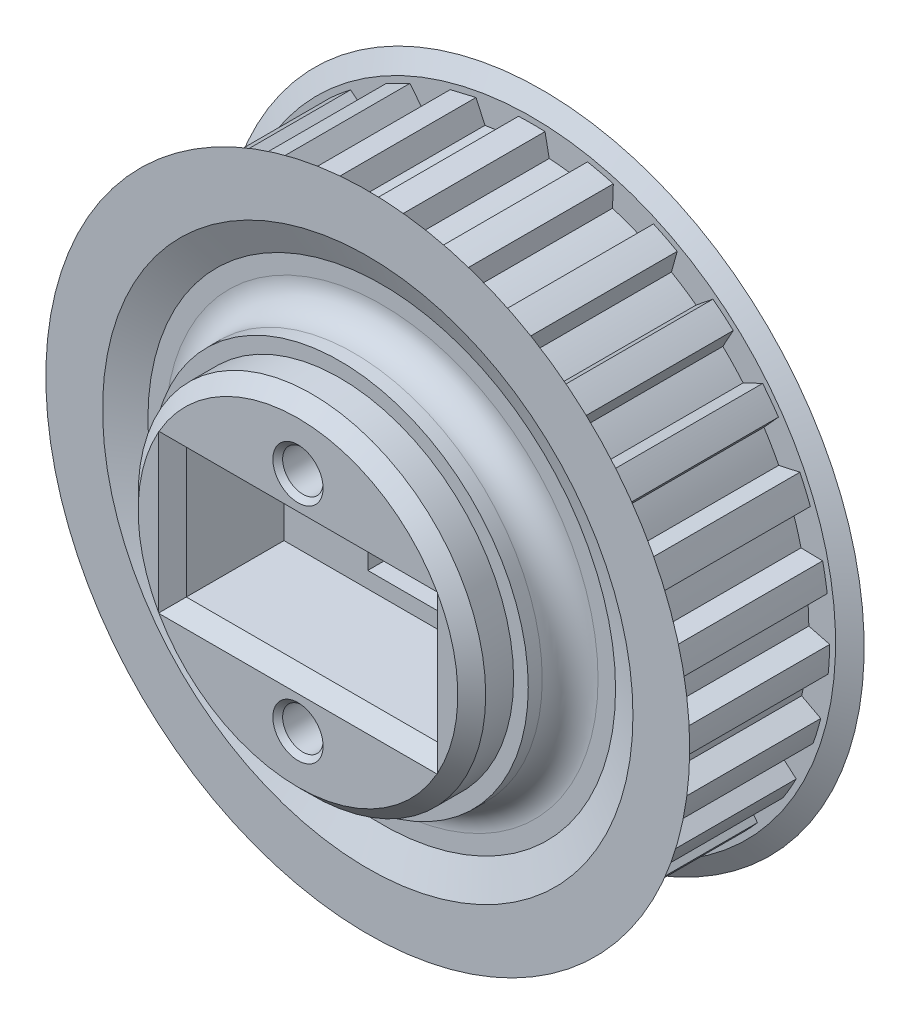
SolidWorks part; units mm, degrees
other "Markup1"
sketch "Sketch8" plane through (-22.8072, 22.8072, -5) normal (-0.0228, 0.8013, -0.5978) x (-0.0343, -0.5983, -0.8006)
material "ABS"
ref_plane "Alzado" through (0, 0, 0) normal (0, 0, 1) x (1, 0, 0)
ref_plane "Planta" through (0, 0, 0) normal (0, 1, 0) x (1, 0, 0)
ref_plane "Vista lateral" through (0, 0, 0) normal (1, 0, 0) x (0, 0, -1)
sketch "Croquis1" plane through (0, 0, 0) normal (0, 0, 1) x (1, 0, 0)
  line L0 (0, 0) -> (0, 14.5885) construction
  line L1 (-0.95, 21.3289) -> (-1.25, 19.8106)
  line L2 (0.95, 21.3289) -> (1.25, 19.8106)
  line L3 (5.8432, 20.5348) -> (5.7849, 18.9883)
  line L4 (3.9944, 20.973) -> (3.3523, 19.5649)
  line L5 (10.4213, 18.6338) -> (10.008, 17.1424)
  line L6 (8.7234, 19.4865) -> (7.7739, 18.2644)
  line L7 (14.4377, 15.7282) -> (13.6916, 14.3723)
  line L8 (12.9822, 16.9495) -> (11.7765, 15.9793)
  line L9 (17.6757, 11.9747) -> (16.637, 10.8274)
  line L10 (16.5411, 13.4987) -> (15.1441, 12.8327)
  line L11 (19.9608, 7.5756) -> (18.6855, 6.6988)
  line L12 (19.2082, 9.3202) -> (17.6953, 8.9943)
  line L13 (21.1698, 2.7681) -> (19.7267, 2.2091)
  line L14 (20.8399, 4.6393) -> (19.2926, 4.6711)
  line L15 (21.2375, -2.1886) -> (19.7044, -2.3998)
  line L16 (21.348, -0.2918) -> (19.8498, 0.096)
  line L17 (20.1604, -7.0273) -> (18.6198, -6.8792)
  line L18 (20.7053, -5.2071) -> (19.3369, -4.4843)
  line L19 (17.9963, -11.4872) -> (16.5315, -10.9878)
  line L20 (18.9463, -9.8417) -> (17.7815, -8.8228)
  line L21 (14.8621, -15.3278) -> (13.5519, -14.5041)
  line L22 (16.166, -13.9457) -> (15.2675, -12.6856)
  line L23 (10.9267, -18.342) -> (9.8417, -17.2384)
  line L24 (12.5141, -17.298) -> (11.9305, -15.8646)
  line L25 (6.4022, -20.3675) -> (5.601, -19.0434)
  line L26 (8.1876, -19.7176) -> (7.9502, -18.1884)
  line L27 (1.5326, -21.2949) -> (1.0583, -19.8218)
  line L28 (3.4197, -21.0743) -> (3.5414, -19.5315)
  line L29 (-3.4197, -21.0743) -> (-3.5414, -19.5315)
  line L30 (-1.5326, -21.2949) -> (-1.0583, -19.8218)
  line L31 (-8.1876, -19.7176) -> (-7.9502, -18.1884)
  line L32 (-6.4022, -20.3675) -> (-5.601, -19.0434)
  line L33 (-12.5141, -17.298) -> (-11.9305, -15.8646)
  line L34 (-10.9267, -18.342) -> (-9.8417, -17.2384)
  line L35 (-16.166, -13.9457) -> (-15.2675, -12.6856)
  line L36 (-14.8621, -15.3278) -> (-13.5519, -14.5041)
  line L37 (-18.9463, -9.8417) -> (-17.7815, -8.8228)
  line L38 (-17.9963, -11.4872) -> (-16.5315, -10.9878)
  line L39 (-20.7053, -5.2071) -> (-19.3369, -4.4843)
  line L40 (-20.1604, -7.0273) -> (-18.6198, -6.8792)
  line L41 (-21.348, -0.2918) -> (-19.8498, 0.096)
  line L42 (-21.2375, -2.1886) -> (-19.7044, -2.3998)
  line L43 (-20.8399, 4.6393) -> (-19.2926, 4.6711)
  line L44 (-21.1698, 2.7681) -> (-19.7267, 2.2091)
  line L45 (-19.2082, 9.3202) -> (-17.6953, 8.9943)
  line L46 (-19.9608, 7.5756) -> (-18.6855, 6.6988)
  line L47 (-16.5411, 13.4987) -> (-15.1441, 12.8327)
  line L48 (-17.6757, 11.9747) -> (-16.637, 10.8274)
  line L49 (-12.9822, 16.9495) -> (-11.7765, 15.9793)
  line L50 (-14.4377, 15.7282) -> (-13.6916, 14.3723)
  line L51 (-8.7234, 19.4865) -> (-7.7739, 18.2644)
  line L52 (-10.4213, 18.6338) -> (-10.008, 17.1424)
  line L53 (-10.4213, 18.6338) -> (-8.7234, 19.4865)
  line L54 (-3.9944, 20.973) -> (-3.3523, 19.5649)
  line L55 (-5.8432, 20.5348) -> (-5.7849, 18.9883)
  line L56 (-5.8432, 20.5348) -> (-3.9944, 20.973)
  arc A0 (-10.008, 17.1424) -> (-11.7765, 15.9793) centre (0, 0) ccw
  arc A1 (3.3523, 19.5649) -> (1.25, 19.8106) centre (0, 0) ccw
  arc A2 (-5.7849, 18.9883) -> (-7.7739, 18.2644) centre (0, 0) ccw
  arc A9 (-12.9822, 16.9495) -> (-14.4377, 15.7282) centre (0, 0) ccw
  arc A10 (-16.5411, 13.4987) -> (-17.6757, 11.9747) centre (0, 0) ccw
  arc A11 (5.8432, 20.5348) -> (3.9944, 20.973) centre (0, 0) ccw
  arc A12 (0.95, 21.3289) -> (-0.95, 21.3289) centre (0, 0) ccw
  arc A16 (10.4213, 18.6338) -> (8.7234, 19.4865) centre (0, 0) ccw
  arc A17 (14.4377, 15.7282) -> (12.9822, 16.9495) centre (0, 0) ccw
  arc A18 (17.6757, 11.9747) -> (16.5411, 13.4987) centre (0, 0) ccw
  arc A19 (19.9608, 7.5756) -> (19.2082, 9.3202) centre (0, 0) ccw
  arc A20 (21.1698, 2.7681) -> (20.8399, 4.6393) centre (0, 0) ccw
  arc A21 (21.2375, -2.1886) -> (21.348, -0.2918) centre (0, 0) ccw
  arc A22 (20.1604, -7.0273) -> (20.7053, -5.2071) centre (0, 0) ccw
  arc A23 (17.9963, -11.4872) -> (18.9463, -9.8417) centre (0, 0) ccw
  arc A24 (14.8621, -15.3278) -> (16.166, -13.9457) centre (0, 0) ccw
  arc A25 (10.9267, -18.342) -> (12.5141, -17.298) centre (0, 0) ccw
  arc A26 (-8.1876, -19.7176) -> (-6.4022, -20.3675) centre (0, 0) ccw
  arc A27 (-12.5141, -17.298) -> (-10.9267, -18.342) centre (0, 0) ccw
  arc A28 (-16.166, -13.9457) -> (-14.8621, -15.3278) centre (0, 0) ccw
  arc A29 (-20.7053, -5.2071) -> (-20.1604, -7.0273) centre (0, 0) ccw
  arc A30 (-21.348, -0.2918) -> (-21.2375, -2.1886) centre (0, 0) ccw
  arc A31 (-20.8399, 4.6393) -> (-21.1698, 2.7681) centre (0, 0) ccw
  arc A32 (-19.2082, 9.3202) -> (-19.9608, 7.5756) centre (0, 0) ccw
  arc A33 (-3.4197, -21.0743) -> (-1.5326, -21.2949) centre (0, 0) ccw
  arc A34 (1.5326, -21.2949) -> (3.4197, -21.0743) centre (0, 0) ccw
  arc A35 (6.4022, -20.3675) -> (8.1876, -19.7176) centre (0, 0) ccw
  arc A36 (7.7739, 18.2644) -> (5.7849, 18.9883) centre (0, 0) ccw
  arc A37 (11.7765, 15.9793) -> (10.008, 17.1424) centre (0, 0) ccw
  arc A39 (-1.25, 19.8106) -> (-3.3523, 19.5649) centre (0, 0) ccw
  arc A43 (15.1441, 12.8327) -> (13.6916, 14.3723) centre (0, 0) ccw
  arc A44 (17.6953, 8.9943) -> (16.637, 10.8274) centre (0, 0) ccw
  arc A45 (19.2926, 4.6711) -> (18.6855, 6.6988) centre (0, 0) ccw
  arc A46 (19.8498, 0.096) -> (19.7267, 2.2091) centre (0, 0) ccw
  arc A47 (19.3369, -4.4843) -> (19.7044, -2.3998) centre (0, 0) ccw
  arc A48 (17.7815, -8.8228) -> (18.6198, -6.8792) centre (0, 0) ccw
  arc A49 (15.2675, -12.6856) -> (16.5315, -10.9878) centre (0, 0) ccw
  arc A50 (11.9305, -15.8646) -> (13.5519, -14.5041) centre (0, 0) ccw
  arc A51 (7.9502, -18.1884) -> (9.8417, -17.2384) centre (0, 0) ccw
  arc A52 (3.5414, -19.5315) -> (5.601, -19.0434) centre (0, 0) ccw
  arc A53 (-1.0583, -19.8218) -> (1.0583, -19.8218) centre (0, 0) ccw
  arc A54 (-5.601, -19.0434) -> (-3.5414, -19.5315) centre (0, 0) ccw
  arc A55 (-9.8417, -17.2384) -> (-7.9502, -18.1884) centre (0, 0) ccw
  arc A56 (-13.5519, -14.5041) -> (-11.9305, -15.8646) centre (0, 0) ccw
  arc A57 (-16.5315, -10.9878) -> (-15.2675, -12.6856) centre (0, 0) ccw
  arc A58 (-18.6198, -6.8792) -> (-17.7815, -8.8228) centre (0, 0) ccw
  arc A59 (-19.7044, -2.3998) -> (-19.3369, -4.4843) centre (0, 0) ccw
  arc A60 (-19.7267, 2.2091) -> (-19.8498, 0.096) centre (0, 0) ccw
  arc A61 (-18.6855, 6.6988) -> (-19.2926, 4.6711) centre (0, 0) ccw
  arc A62 (-16.637, 10.8274) -> (-17.6953, 8.9943) centre (0, 0) ccw
  arc A63 (-13.6916, 14.3723) -> (-15.1441, 12.8327) centre (0, 0) ccw
  arc A71 (-18.9463, -9.8417) -> (-17.9963, -11.4872) centre (0, 0) ccw
  circle A72 centre (0, 0) radius 1.5
  point P151 (0, 0)
  dimension "D1" = 21.35
  dimension "D6" = 3
  dimension "D5" = 1.5
  dimension "D2" = 2.5
  dimension "D3" = 1.9
  dimension "D4" = 27
extrude "Saliente-Extruir1" add sketch "Croquis1" along normal blind 11
sketch "Croquis2" plane through (0, 0, 11) normal (0, 0, 1) x (1, 0, 0)
  circle A0 centre (0, 0) radius 23.5
  circle A1 centre (0, 0) radius 1.5
  circle A2 centre (0, 0) radius 1.5 construction
  dimension "D1" = 47
extrude "Saliente-Extruir2" add sketch "Croquis2" along normal blind 0.75
sketch "Croquis3" plane through (0, 0, 11.75) normal (0, 0, 1) x (1, 0, 0)
  circle A0 centre (0, 0) radius 1.5
  circle A1 centre (0, 0) radius 12.45
  circle A3 centre (0, 0) radius 1.5 construction
  dimension "D1" = 24.9
sketch "Croquis4" plane through (0, 0, 0) normal (0, 0, -1) x (-1, 0, 0)
  circle A0 centre (0, 0) radius 1.5
  circle A1 centre (0, 0) radius 12.35
  circle A2 centre (0, 0) radius 1.5 construction
  dimension "D1" = 24.7
extrude "Saliente-Extruir4" add sketch "Croquis4" along normal blind 5.5
sketch "Croquis6" plane through (0, 0, 0) normal (0, 0, -1) x (-1, 0, 0)
  circle A0 centre (0, 0) radius 23.5
  circle A1 centre (0, 0) radius 1.5
  circle A2 centre (0, 0) radius 1.5 construction
  dimension "D1" = 47
extrude "Saliente-Extruir6" add sketch "Croquis6" along normal blind 0.75
sketch "Sketch6" plane through (0, 0, -0.75) normal (0, 0, -1) x (-1, 0, 0)
  circle A0 centre (0, 0) radius 12.35
  circle A1 centre (0, 0) radius 18.5
  circle A2 centre (0, 0) radius 12.35 construction
  dimension "D1" = 37
extrude "Cut-Extrude3" cut sketch "Sketch6" against normal blind 1
sketch "Croquis5" plane through (0, 0, 0.25) normal (0, 0, -1) x (-1, 0, 0)
  circle A0 centre (0, 0) radius 1.5
  circle A1 centre (0, 0) radius 13.5
  circle A2 centre (0, 0) radius 1.5 construction
  dimension "D1" = 27
extrude "Saliente-Extruir5" add sketch "Croquis5" along normal blind 2.75
chamfer "Chaflán2" distance 1 angle 60 2 edges at (-23.5, 0, 0) (23.5, 0, 11)
extrude "Saliente-Extruir7" add sketch "Croquis3" along normal blind 5
sketch "Sketch7" plane through (0, 0, 11.75) normal (0, 0, 1) x (1, 0, 0)
  circle A0 centre (0, 0) radius 12.45
  circle A1 centre (0, 0) radius 19
  circle A2 centre (0, 0) radius 12.45 construction
  dimension "D1" = 38
extrude "Cut-Extrude4" cut sketch "Sketch7" against normal blind 1
chamfer "Chaflán4" distance 1 angle 45 1 edges at (12.45, 0, 16.75)
sketch "Croquis7" plane through (0, 0, 10.75) normal (0, 0, 1) x (1, 0, 0)
  circle A0 centre (0, 0) radius 1.5
  circle A1 centre (0, 0) radius 13.5
  circle A2 centre (0, 0) radius 1.5 construction
  dimension "D1" = 27
extrude "Saliente-Extruir8" add sketch "Croquis7" along normal blind 3
sketch "Croquis8" plane through (0, 0, 0) normal (0, 0, 1) x (1, 0, 0)
  line L0 (0, 0) -> (6.706, 0) construction
  line L1 (-3, 3.5) -> (3, 3.5)
  line L2 (-3, 3.5) -> (-3, -3.5)
  line L3 (-3, -3.5) -> (3, -3.5)
  line L4 (3, 3.5) -> (3, -3.5)
  line L5 (-3, 3.5) -> (3, -3.5) construction
  line L6 (-3, -3.5) -> (3, 3.5) construction
  circle A0 centre (0, 8) radius 1.45
  circle A1 centre (0, -8) radius 1.45
  point P0 (0, 0)
  dimension "D1" = 2.9
  dimension "D2" = 7
  dimension "D3" = 6
  dimension "D4" = 16
extrude "Cortar-Extruir1" cut sketch "Croquis8" against normal through all both and the other way through all
sketch "Croquis10" plane through (0, 0, 16.75) normal (0, 0, 1) x (1, 0, 0)
  line L1 (9, 4.65) -> (-9, 4.65)
  line L2 (9, 4.65) -> (9, -4.65)
  line L3 (9, -4.65) -> (-9, -4.65)
  line L4 (-9, 4.65) -> (-9, -4.65)
  line L5 (9, 4.65) -> (-9, -4.65) construction
  line L6 (9, -4.65) -> (-9, 4.65) construction
  point P0 (0, 0)
  dimension "D1" = 9.3
  dimension "D2" = 18
extrude "Cortar-Extruir3" cut sketch "Croquis10" against normal blind 8
chamfer "Chaflán5" distance 1 angle 45 8 edges at (-3, 0, -5.5) (0, 3.5, -5.5) (3, 0, -5.5) (0, -3.5, -5.5) (9, 0, 16.75) (0, 4.65, 16.75) (-9, 0, 16.75) (0, -4.65, 16.75)
sketch "Sketch1" plane through (0, 0, -5.5) normal (0, 0, -1) x (-1, 0, 0)
  circle A0 centre (0, 0) radius 12.35
  circle A1 centre (0, 0) radius 12.35 construction
  circle A2 centre (0, 8) radius 1.45
  circle A3 centre (0, -8) radius 1.45
  circle A4 centre (0, 8) radius 1.45 construction
extrude "Boss-Extrude1" add sketch "Sketch1" against normal blind 5
sketch "Sketch2" plane through (0, 0, -5.5) normal (0, 0, -1) x (-1, 0, 0)
  line L0 (0, 17.274) -> (0, -20.0751) construction
  line L1 (-6.5, 0) -> (6.5, 0) construction
  circle A0 centre (-6.5, 0) radius 1.45
  circle A1 centre (6.5, 0) radius 1.45
  dimension "D1" = 2.9
  dimension "D2" = 13
extrude "Cut-Extrude1" cut sketch "Sketch2" against normal through all
sketch "Sketch4" plane through (0, 0, 16.75) normal (0, 0, 1) x (1, 0, 0)
  line L0 (-3, -3.5) -> (3, -3.5) construction
  line L1 (3, 3.5) -> (-3, 3.5)
  line L2 (3, 3.5) -> (3, -3.5)
  line L3 (3, -3.5) -> (-3, -3.5)
  line L4 (-3, 3.5) -> (-3, -3.5)
  line L5 (3, 3.5) -> (-3, -3.5) construction
  line L6 (3, -3.5) -> (-3, 3.5) construction
  point P0 (0, 0)
  dimension "D1" = 6
extrude "Cut-Extrude2" cut sketch "Sketch4" against normal blind 30
chamfer "Chamfer3" distance 1 angle 45 4 edges at (-3, 0, -5.5) (0, 3.5, -5.5) (3, 0, -5.5) (0, -3.5, -5.5)
chamfer "Chamfer2" distance 0.75 angle 45 1 edges at (-12.35, 0, -5.5)
chamfer "Chamfer4" distance 1 angle 66 2 edges at (19, 0, 10.75) (-18.5, 0, 0.25)
chamfer "Chamfer5" distance 0.35 angle 45 8 edges at (1.45, -8, -5.5) (-5.05, 0, -5.5) (5.05, 0, -5.5) (1.45, 8, -5.5) (-7.95, 0, 8.75) (1.45, 8, 16.75) (5.05, 0, 8.75) (1.45, -8, 16.75)
fillet "Fillet1" radius 2 2 edges at (-13.5, 0, 0.25) (13.5, 0, 10.75)
